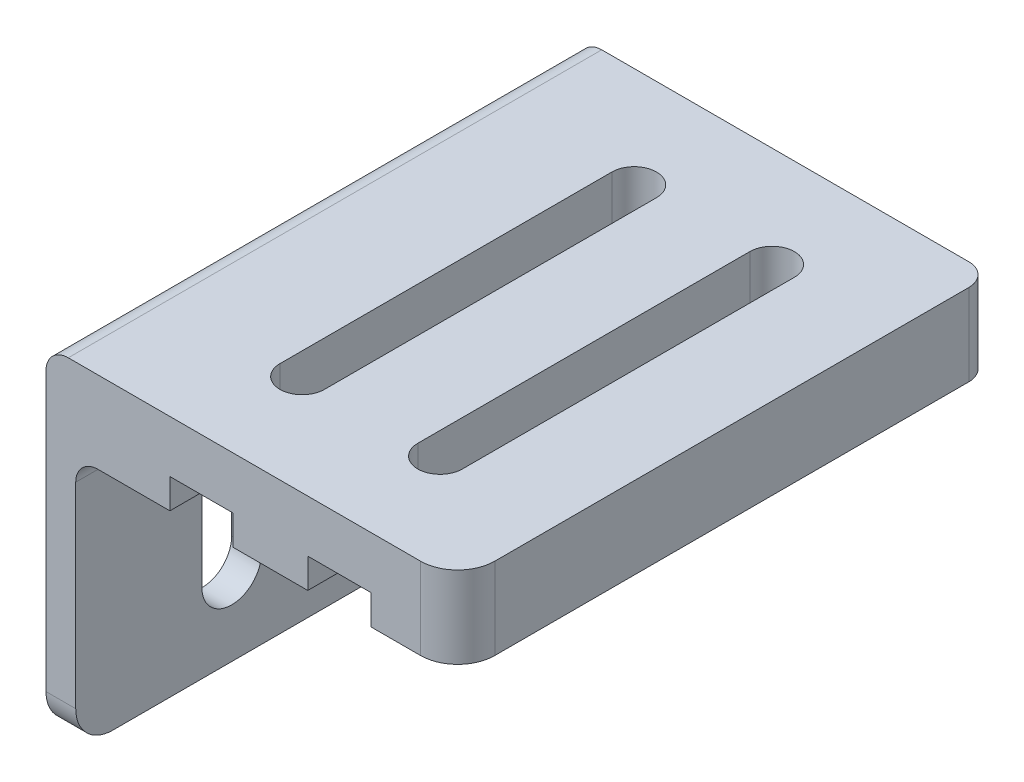
SolidWorks part; units mm, degrees
ref_plane "Front Plane" through (0, 0, 0) normal (0, 0, 1) x (1, 0, 0)
ref_plane "Top Plane" through (0, 0, 0) normal (0, 1, 0) x (1, 0, 0)
ref_plane "Right Plane" through (0, 0, 0) normal (1, 0, 0) x (0, 0, -1)
sketch "Sketch2" plane through (93.4, 0, 0) normal (-1, 0, 0) x (0, 0, 1)
  line L0 (5.2578, -173.8493) -> (-15.7255, -173.8493) construction
  line L1 (5.2578, -173.8493) -> (26.241, -173.8493) construction
  line L2 (5.2578, -173.8493) -> (5.2578, -155.7) construction
  line L3 (-15.7255, -189.7) -> (26.241, -189.7) construction
  line L4 (-15.7255, -189.9) -> (26.241, -189.9)
  line L5 (26.241, -193.9) -> (-15.7255, -193.9)
  line L6 (26.241, -193.9) -> (26.241, -144.5)
  line L8 (-15.7255, -193.9) -> (-15.7255, -144.5)
  line L9 (-15.7255, -155.5) -> (26.241, -155.5)
  line L10 (-15.7255, -144.5) -> (26.241, -144.5)
  line L11 (-15.7255, -155.7) -> (26.241, -155.7) construction
  circle A1 centre (5.2578, -173.8493) radius 4
  point P13 (0, 0)
  dimension "D1" = 8
  dimension "D2" = 18.1493
  dimension "D3" = 34
  dimension "D4" = 41.9666
  dimension "D5" = 0.2
  dimension "D6" = 4
  dimension "D7" = 155.7
  dimension "D8" = 15.7255
  dimension "D9" = 0.2
  dimension "D10" = 11
extrude "Boss-Extrude1" add sketch "Sketch2" along normal blind 4 from offset 0.2 contours L10 L8 L9 L6 | L9 L8 L4 L6 A1 | L8 L5 L6 L4 region at (93.4, -172.7, -15.1829) region at (93.4, -191.9, 5.2578) region at (93.4, -150, 5.2578)
extrude "Boss-Extrude2" add sketch "Sketch2<3>" along normal up to next and the other way blind 60.2 contours L10 L8 L9 L6 | L8 L5 L6 L4 region at (93.4, -191.9, 5.2578) region at (93.4, -150, 5.2578)
sketch "Sketch2<3>" plane through (93.4, 0, 0) normal (-1, 0, 0) x (0, 0, 1) same geometry as "Sketch2"
fillet "Fillet1" radius 3 5 edges at (153.6, -191.9, 26.241) (153.6, -191.9, -15.7255) (93.2, -155.5, 5.2578) (89.2, -193.9, 5.2578) (93.2, -189.9, 5.2578)
sketch "Sketch3" plane through (0, 0, 26.241) normal (0, 0, 1) x (1, 0, 0)
  line L0 (89.2, -144.5) -> (153.6, -144.5) construction
  line L1 (153.6, -144.5) -> (144.6, -144.5)
  line L2 (153.6, -144.5) -> (153.6, -155.7)
  line L3 (153.6, -155.7) -> (144.6, -155.7)
  line L4 (144.6, -144.5) -> (144.6, -155.7)
  dimension "D1" = 9
extrude "Cut-Extrude1" cut sketch "Sketch3" against normal blind 24.029
sketch "Sketch4" plane through (153.6, 0, 0) normal (1, 0, 0) x (0, 0, -1)
  line L0 (15.7255, -190.9) -> (15.7255, -144.5) construction
  line L1 (15.7255, -155.5) -> (-55.9337, -155.5)
  line L2 (15.7255, -155.5) -> (15.7255, -135.8096)
  line L3 (15.7255, -135.8096) -> (-55.9337, -135.8096)
  line L4 (-55.9337, -155.5) -> (-55.9337, -135.8096)
  line L9 (-9.6862, -150.8871) -> (-39.2974, -150.8871) construction
  line L10 (-9.6862, -140.5148) -> (-39.2974, -140.5148) construction
  line L12 (-9.6862, -142.5148) -> (-39.2974, -142.5148) construction
  line L13 (-9.6862, -148.8871) -> (-39.2974, -148.8871) construction
  arc A4 (-39.2974, -140.5148) -> (-39.2974, -150.8871) centre (-39.2974, -145.7009) ccw construction
  arc A5 (-9.6862, -150.8871) -> (-9.6862, -140.5148) centre (-9.6862, -145.7009) ccw construction
  arc A6 (-39.2974, -142.5148) -> (-39.2974, -148.8871) centre (-39.2974, -145.7009) ccw construction
  arc A7 (-9.6862, -148.8871) -> (-9.6862, -142.5148) centre (-9.6862, -145.7009) ccw construction
  circle A8 centre (-39.2974, -145.7009) radius 3.1862
  circle A9 centre (-9.6862, -145.7009) radius 3.1862
  dimension "D1" = 2
extrude "Boss-Extrude3" add sketch "Sketch4" against normal blind 4
fillet "Fillet2" radius 3 3 edges at (149.6, -144.5, -6.7568) (151.6, -135.8096, -15.7255) (151.6, -135.8096, 55.9337)
sketch "Sketch5" plane through (0, -144.5, 0) normal (0, 1, 0) x (1, 0, 0)
  line L0 (89.2, -26.241) -> (144.6, -26.241) construction
  line L1 (144.6, -26.241) -> (89.2, -26.241)
  line L2 (144.6, -26.241) -> (144.6, -56.0614)
  line L3 (144.6, -56.0614) -> (89.2, -56.0614)
  line L4 (89.2, -26.241) -> (89.2, -56.0614)
  line L6 (144.6, -2.212) -> (144.6, -26.241) construction
extrude "Boss-Extrude4" add sketch "Sketch5" against normal up to vertex (11 mm away) up to point (144.6, -155.5, 26.241)
fillet "Fillet3" radius 3 2 edges at (144.6, -150, 56.0614) (89.2, -144.5, 20.168)
sketch "Sketch7" plane through (0, 0, -15.7255) normal (0, 0, -1) x (-1, 0, 0)
  line L0 (-128.6778, -153.5) -> (-128.6778, -147.6036) construction
  line L1 (-153.6, -155.5) -> (-96.2, -155.5) construction
  line L2 (-119.4, -144.5) -> (-119.4, -155.5) construction
  line L3 (-132.9278, -155.5) -> (-124.4278, -155.5)
  line L4 (-132.9278, -155.5) -> (-132.9278, -151.5)
  line L5 (-132.9278, -151.5) -> (-124.4278, -151.5)
  line L6 (-124.4278, -155.5) -> (-124.4278, -151.5)
  line L7 (-132.9278, -155.5) -> (-124.4278, -151.5) construction
  line L8 (-132.9278, -151.5) -> (-124.4278, -155.5) construction
  line L9 (-92.2, -144.5) -> (-146.6, -144.5) construction
  line L10 (-105.8722, -151.5) -> (-114.3722, -155.5) construction
  line L11 (-105.8722, -155.5) -> (-114.3722, -151.5) construction
  line L12 (-110.1222, -153.5) -> (-110.1222, -147.6036) construction
  line L13 (-114.3722, -155.5) -> (-114.3722, -151.5)
  line L14 (-105.8722, -151.5) -> (-114.3722, -151.5)
  line L15 (-105.8722, -155.5) -> (-105.8722, -151.5)
  line L16 (-105.8722, -155.5) -> (-114.3722, -155.5)
  dimension "D1" = 4
  dimension "D2" = 8.5
extrude "Cut-Extrude2" cut sketch "Sketch7" against normal through all both and the other way through all
fillet "Fillet6" radius 2 1 edges at (144.6, -150, 2.212)
sketch "Sketch8" plane through (0, -144.5, 0) normal (0, 1, 0) x (1, 0, 0)
  line L0 (105.8722, 15.7255) -> (114.3722, 15.7255) construction
  line L1 (114.3722, 15.7255) -> (114.3722, -56.0614) construction
  line L2 (114.3722, -56.0614) -> (105.8722, -56.0614) construction
  line L3 (105.8722, -56.0614) -> (105.8722, 15.7255) construction
  line L8 (105.8722, 15.7255) -> (114.3722, 15.7255) construction
  line L9 (114.3722, 15.7255) -> (114.3722, -56.0614) construction
  line L10 (114.3722, -56.0614) -> (105.8722, -56.0614) construction
  line L11 (105.8722, -56.0614) -> (105.8722, 15.7255) construction
  line L16 (110.1222, 15.7255) -> (110.1222, -56.0614) construction
  line L17 (119.4, 15.7255) -> (119.4, -4.8632) construction
  line L18 (110.1222, 2.1725) -> (110.1222, -42.5084) construction
  line L19 (113.1222, 2.1725) -> (113.1222, -42.5084)
  line L20 (107.1222, 2.1725) -> (107.1222, -42.5084)
  line L21 (92.2, 15.7255) -> (146.6, 15.7255) construction
  line L22 (128.6778, 2.1725) -> (128.6778, -42.5084) construction
  line L23 (125.6778, 2.1725) -> (125.6778, -42.5084)
  line L24 (131.6778, 2.1725) -> (131.6778, -42.5084)
  arc A0 (113.1222, 2.1725) -> (107.1222, 2.1725) centre (110.1222, 2.1725) ccw
  arc A1 (107.1222, -42.5084) -> (113.1222, -42.5084) centre (110.1222, -42.5084) ccw
  arc A2 (125.6778, 2.1725) -> (131.6778, 2.1725) centre (128.6778, 2.1725) cw
  arc A3 (131.6778, -42.5084) -> (125.6778, -42.5084) centre (128.6778, -42.5084) cw
  point P14 (110.1222, -20.168)
  point P19 (128.6778, -20.168)
  point P20 (110.1222, -20.168)
  dimension "D1" = 6
extrude "Cut-Extrude3" cut sketch "Sketch8" against normal up to next
sketch "Sketch9" plane through (0, -135.8096, 0) normal (0, 1, 0) x (1, 0, 0)
  line L0 (144.6, -4.212) -> (144.6, -53.0614) construction
  line L1 (144.6, 47.1157) -> (144.6, -77.5818)
  line L2 (144.6, 47.1157) -> (190.1821, 46.6078)
  line L3 (190.1821, 46.6078) -> (185.5446, -56.6744)
  line L4 (185.5446, -56.6744) -> (144.6, -77.5818)
extrude "Cut-Extrude4" cut sketch "Sketch9" against normal through all both and the other way through all
fillet "Fillet7" radius 5 1 edges at (144.6, -150, -15.7255)
sketch "Sketch10" plane through (89.2, 0, 0) normal (-1, 0, 0) x (0, 0, 1)
  line L1 (26.241, -155.5) -> (56.0614, -155.5) construction
  line L2 (26.241, -189.9) -> (56.0614, -189.9)
  line L3 (26.241, -190.9) -> (26.241, -155.5) construction
  line L4 (26.241, -189.9) -> (26.241, -155.5)
  line L5 (26.241, -155.5) -> (56.0614, -155.5)
  line L6 (26.241, -189.9) -> (26.241, -186.9) construction
  line L7 (26.241, -193.9) -> (26.241, -189.9) construction
  line L10 (56.0614, -155.5) -> (56.0614, -189.9)
extrude "Boss-Extrude5" add sketch "Sketch10" against normal up to vertex (4 mm away) up to point (93.2, -186.9, 26.241)
sketch "Sketch11" plane through (0, 0, 26.241) normal (0, 0, 1) x (1, 0, 0)
  line L2 (93.2, -155.5) -> (93.2, -158.5)
  line L3 (96.2, -155.5) -> (93.2, -155.5)
  line L4 (93.2, -155.5) -> (93.2, -158.5)
  line L5 (96.2, -155.5) -> (93.2, -155.5)
  arc A1 (96.2, -155.5) -> (93.2, -158.5) centre (96.2, -158.5) ccw
  arc A3 (96.2, -155.5) -> (93.2, -158.5) centre (96.2, -158.5) ccw
  dimension "D1" = 0
extrude "Boss-Extrude6" add sketch "Sketch11" along normal up to surface (29.8204 mm away) up to face at (112.9852, -156.9786, 56.0614)
sketch "Sketch14" plane through (89.2, 0, 0) normal (-1, 0, 0) x (0, 0, 1)
  line L0 (5.2578, -168.4085) -> (5.2578, -179.2901) construction
  line L1 (9.2578, -168.4085) -> (9.2578, -179.2901)
  line L2 (1.2578, -168.4085) -> (1.2578, -179.2901)
  circle A0 centre (5.2578, -173.8493) radius 4 construction
  circle A1 centre (5.2578, -173.8493) radius 4 construction
  arc A2 (9.2578, -168.4085) -> (1.2578, -168.4085) centre (5.2578, -168.4085) ccw
  arc A3 (1.2578, -179.2901) -> (9.2578, -179.2901) centre (5.2578, -179.2901) ccw
  point P5 (5.2578, -173.8493)
extrude "Cut-Extrude5" cut sketch "Sketch14" against normal through all both and the other way through all
sketch "Sketch15" plane through (89.2, 0, 0) normal (-1, 0, 0) x (0, 0, 1)
  line L1 (61.4991, -189.9) -> (-17.2284, -189.9)
  line L2 (61.4991, -189.9) -> (61.4991, -203.7571)
  line L3 (61.4991, -203.7571) -> (-17.2284, -203.7571)
  line L4 (-17.2284, -189.9) -> (-17.2284, -203.7571)
extrude "Cut-Extrude6" cut sketch "Sketch15" against normal through all both and the other way through all
sketch "Sketch16" plane through (0, -189.9, 0) normal (0, -1, 0) x (1, 0, 0)
  line L0 (93.2, 26.241) -> (93.2, -15.7255) construction
  line L1 (93.2, 37.1066) -> (93.2, -15.7255)
  line L3 (93.2, 37.1066) -> (106.6333, 37.1066)
  line L4 (93.2, 37.1066) -> (93.2, -15.7255)
  line L5 (93.2, -15.7255) -> (106.6333, -15.7255)
  line L6 (106.6333, 37.1066) -> (106.6333, -15.7255)
  line M1 (89.2, -15.7255) -> (96.2, -15.7255)
  line M2 (96.2, -15.7255) -> (96.2, 26.241)
extrude "Cut-Extrude8" cut sketch "Sketch16" against normal up to next contours L1 M1 M2 region at (99.9167, -189.9, 10.6905)
fillet "Fillet8" radius 5 2 edges at (91.2, -189.9, 56.0614) (91.2, -189.9, -15.7255)
mirror "Mirror1" about plane through (144.6, -155.5, 56.0614) normal (0, 0, 1) of bodies 121
delete or keep bodies "Body-Delete/Keep 1" type delete bodies bodies 121
